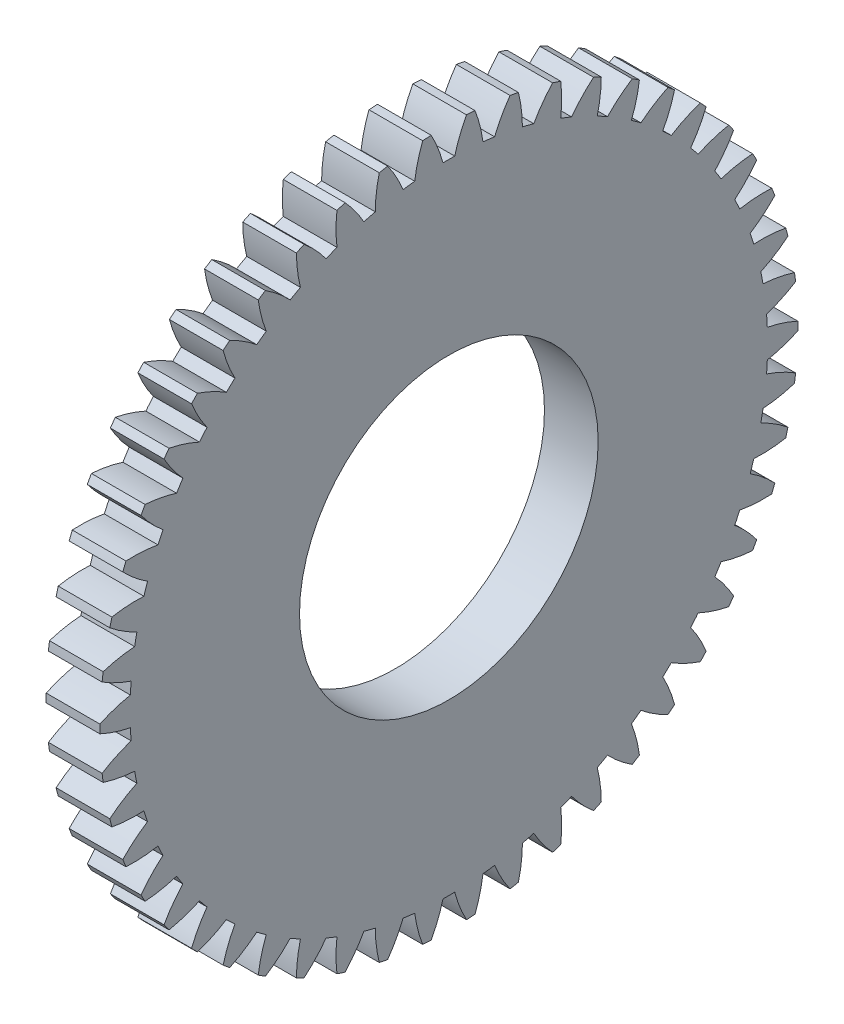
SolidWorks part; units mm, degrees
ref_plane "Plane1" through (0, 0, 0) normal (0, 0, 1) x (1, 0, 0)
ref_plane "Plane2" through (0, 0, 0) normal (0, 1, 0) x (1, 0, 0)
ref_plane "Plane3" through (0, 0, 0) normal (1, 0, 0) x (0, 0, -1)
sketch "HoldingSke" plane through (0, 0, 0) normal (0, 1, 0) x (1, 0, 0)
  line L0 (0, 0) -> (0.6428, -0.766)
  line L1 (-15, 0) -> (100, 0) construction
  line L2 (0, 0) -> (-2.1039, 2.3779)
  line L3 (0, 0) -> (-11.863, 4.5341)
  line L4 (0, 0) -> (5.5511, 6.6156)
  line L5 (0, 0) -> (-46.8476, -17.4728)
  line L6 (0, 0) -> (-3.3159, -2.2372)
  line L7 (-2.1039, 2.3779) -> (8.6586, 51.2059)
  line L8 (-76.2, 54.61) -> (-75.3, 54.61)
  line L9 (-71.009, 38.7566) -> (-53.1078, 45.2721)
  line L10 (-76.2, 71.12) -> (104.1128, 71.12)
  line L11 (0, 0) -> (-4, 0)
  line L12 (-76.2, 101.6) -> (-76.162, 101.6)
  line L13 (24.9733, 27.94) -> (52.9518, 28.4284)
  line L14 (24.9733, 27.94) -> (24.9743, 27.94)
  line L15 (24.9733, 27.94) -> (100.4006, 29.5858)
  line L16 (-63.627, -1) -> (-12.827, -1)
  circle A0 centre (0, 0) radius 2.5
  circle A1 centre (0, 0) radius 23.749
  circle A2 centre (0, 0) radius 37.5
  circle A3 centre (0, 0) radius 2.5
  dimension "MHD" = 47.498
  dimension "Hub_dia" = 75
  dimension "Bore" = 5
  dimension "MBD" = 5
  dimension "Num_teeth" = 50
  dimension "Pitch" = 1
  dimension "Overall_len" = 50
  dimension "Show_teeth" = 50
  dimension "Thickness" = 4
  dimension "OAL" = 50.0001
  dimension "T_dim" = 0.9
  dimension "Ap" = 20
  dimension "H" = 19.05
  dimension "Pitch_radius" = 180.3128
  dimension "Width" = 4
  dimension "Backlash" = 0.038
  dimension "Addendum_fac" = 1
  dimension "Dedendum_fac" = 1.25
  dimension "Clearance_fac" = 0.25
  dimension "Dedendum_add" = 0.001
  dimension "Module" = 1
sketch "BasProSke" plane through (0, 0, 0) normal (0, 1, 0) x (1, 0, 0)
  line L0 (-10, 0) -> (60, 0) construction
  line L1 (0, 0) -> (0, 26)
  line L2 (0, 0) -> (4, 0)
  line L3 (4, 0) -> (4, 26)
  line L4 (4, 26) -> (0, 26)
  dimension "Thickness" = 4
  dimension "Diameter" = 52
revolve "Base-Revolve" add sketch "BasProSke" angle 360 about L0
sketch "TooCutSke" plane through (0, 0, 0) normal (1, 0, 0) x (0, 0, -1)
  line L1 (0, 0) -> (0, 107) construction
  line L2 (0, 0) -> (-0.8518, 24.9855) construction
  line L3 (0, 0) -> (-3.1382, 49.8807) construction
  line L4 (-0.8518, 24.9855) -> (-1.5691, 24.9404) construction
  arc A0 (0.4377, 23.745) -> (-0.4377, 23.745) centre (0, 0) ccw
  arc A1 (1.3294, 25.9914) -> (-1.3294, 25.9914) centre (0, 0) ccw
  circle A2 centre (0, 0) radius 25 construction
  circle A3 centre (0, 0) radius 23.4923 construction
  arc A4 (-0.4377, 23.745) -> (-1.3294, 25.9914) centre (-10.1099, 21.2056) ccw
  arc A5 (1.3294, 25.9914) -> (0.4377, 23.745) centre (10.1099, 21.2056) ccw
  dimension "Root_dia" = 47.498
  dimension "Overcut_dia" = 52.0508
  dimension "Pitch_dia" = 50
  dimension "Base_dia" = 46.9846
  dimension "Flank_rad" = 10
  dimension "Half_ang" = 3.6
  dimension "Half_CT" = 0.7188
extrude "ToothCut" cut sketch "TooCutSke" along normal through all
fillet "Breaks" [suppressed] radius 0.02 tangent propagation no
fillet "RootFillets" [suppressed] radius 0.251
pattern_circular "TeethCuts" count 50 every 7.2 about axis through (-10, 0, 0) along (1, 0, 0) of "ToothCut", "RootFillets", "Breaks"
sketch "HubNeaOneSke" plane through (0, 0, 0) normal (-1, 0, 0) x (0, 0, 1)
  circle A0 centre (0, 0) radius 23.749
  dimension "Diameter" = 47.498
extrude "HubNearOne" [suppressed] add sketch "HubNeaOneSke" along normal blind 46.0001
sketch "HubNeaBotSke" plane through (0, 0, 0) normal (-1, 0, 0) x (0, 0, 1)
  circle A0 centre (0, 0) radius 23.749
  dimension "Diameter" = 47.498
extrude "HubNearBoth" [suppressed] add sketch "HubNeaBotSke" along normal blind 23
ref_plane "FarPln" through (4, 0, 0) normal (1, 0, 0) x (0, 0, -1)
sketch "HubFarSke" plane through (4, 0, 0) normal (1, 0, 0) x (0, 0, -1)
  circle A0 centre (0, 0) radius 23.749
  dimension "Diameter" = 47.498
extrude "HubFar" [suppressed] add sketch "HubFarSke" along normal blind 23
sketch "BorSke" plane through (0, 0, 0) normal (1, 0, 0) x (0, 0, -1)
  circle A0 centre (0, 0) radius 2.5
  dimension "Diameter" = 5
extrude "Bore" cut sketch "BorSke" along normal mid plane 100.0001
sketch "KeySke" plane through (0, 0, 0) normal (1, 0, 0) x (0, 0, -1)
  line L0 (-1, 0) -> (-1, 3.4)
  line L1 (-1, 3.4) -> (1, 3.4)
  line L2 (1, 3.4) -> (1, 0)
  line L3 (0, 0) -> (0, 34) construction
  line L4 (-1, 0) -> (1, 0)
  dimension "Offset" = 3.4
  dimension "Width" = 2
extrude "Keyway" [suppressed] cut sketch "KeySke" along normal mid plane 100.0001
pattern_circular "Keyway2" [suppressed] count 2 every 90 about axis through (-10, 0, 0) along (1, 0, 0) reverse direction yes
sketch "Sketch1" plane through (0, 0, 0) normal (-1, 0, 0) x (0, 0, 1)
  circle A0 centre (0, 0) radius 11.125
  circle A1 centre (0, 0) radius 2.5 construction
  dimension "D1" = 22.25
extrude "Cut-Extrude1" cut sketch "Sketch1" against normal up to next
equation "' \"Module@HoldingSke\" = 6.35"
equation "' \"Num_teeth@HoldingSke\" = 12"
equation "' \"Ap@HoldingSke\" =  20"
equation "' \"Ap@HoldingSke\" = 20"
equation "' \"Width@HoldingSke\" = 0.5 * 25.4"
equation "' \"Hub_dia@HoldingSke\"= 1 * 25.4"
equation "' \"Hub_dia@HoldingSke\" = 1 * 25.4"
equation "' \"Overall_len@HoldingSke\" = 1.0 * 25.4"
equation "' \"Bore@HoldingSke\" = 0.75 * 25.4"
equation "' \"T_dim@HoldingSke\" = 0.1 * 25.4"
equation "' \"Width@KeySke\" = 0.25 * 25.4"
equation "' \"Show_teeth@HoldingSke\" = 13"
equation "' \"Backlash@HoldingSke\" = 0.009 * 25.4"
equation "' \"Addendum_fac@HoldingSke\" = 1.0"
equation "' \"Dedendum_fac@HoldingSke\" = 1.25"
equation "' \"Dedendum_add@HoldingSke\" = 0.00005 * 25.4"
equation "' \"Clearance_fac@HoldingSke\" = 0.25"
equation "\"Pitch@HoldingSke\" = 1 / \"Module@HoldingSke\""
equation "\"Overcut_dia@TooCutSke\" = (\"Num_teeth@HoldingSke\" + 2 * \"Addendum_fac@HoldingSke\") / \"Pitch@HoldingSke\" + 0.002 * 25.4"
equation "\"Pitch_dia@TooCutSke\" = \"Num_teeth@HoldingSke\" / \"Pitch@HoldingSke\""
equation "\"Base_dia@TooCutSke\" = \"Num_teeth@HoldingSke\" / \"Pitch@HoldingSke\" * cos((\"Ap@HoldingSke\"  * 3.14159265 / 180))"
equation "\"Root_dia@TooCutSke\" = (\"Num_teeth@HoldingSke\" + 2) / \"Pitch@HoldingSke\" - 2 * (\"Addendum_fac@HoldingSke\" + \"Dedendum_fac@HoldingSke\") / \"Pitch@HoldingSke\" - \"Dedendum_add@HoldingSke\" * 2"
equation "\"Half_ang@TooCutSke\" = 180 / \"Num_teeth@HoldingSke\""
equation "\"Half_CT@TooCutSke\" = \"Num_teeth@HoldingSke\" / \"Pitch@HoldingSke\" * sin((3.14159265 / 2 / \"Num_teeth@HoldingSke\")) / 2 - 7 * \"Backlash@HoldingSke\" / 4"
equation "\"Flank_rad@TooCutSke\" = \"Num_teeth@HoldingSke\" / \"Pitch@HoldingSke\" / 5"
equation "\"Radius@RootFillets\" = \"Clearance_fac@HoldingSke\" / \"Pitch@HoldingSke\" + \"Dedendum_add@HoldingSke\""
equation "\"Break_rad@Breaks\" = 0.02 / \"Pitch@HoldingSke\""
equation "\"Thickness@HoldingSke\" = \"Width@HoldingSke\""
equation "\"OAL@HoldingSke\" = \"Thickness@HoldingSke\""
equation "\"MHD@HoldingSke\" = (\"Num_teeth@HoldingSke\" + 2) / \"Pitch@HoldingSke\" - 2 * (\"Addendum_fac@HoldingSke\" + \"Dedendum_fac@HoldingSke\")  / \"Pitch@HoldingSke\" - \"Dedendum_add@HoldingSke\" * 2"
equation "\"MBD@HoldingSke\" = (\"Num_teeth@HoldingSke\" + 2) / \"Pitch@HoldingSke\" - 2 * (\"Addendum_fac@HoldingSke\" + \"Dedendum_fac@HoldingSke\")  / \"Pitch@HoldingSke\" - \"Dedendum_add@HoldingSke\" * 2 - 0.002 * 25.4"
equation "\"MHD@HoldingSke\" = ((sgn( \"MHD@HoldingSke\" - \"Hub_dia@HoldingSke\" )-1)*( \"MHD@HoldingSke\" - \"Hub_dia@HoldingSke\" ))/-2+ \"Hub_dia@HoldingSke\""
equation "\"MBD@HoldingSke\" = ((sgn( \"MBD@HoldingSke\" - \"Bore@HoldingSke\" )-1)*( \"MBD@HoldingSke\" - \"Bore@HoldingSke\" ))/-2+ \"Bore@HoldingSke\""
equation "\"OAL@HoldingSke\" = ((sgn( \"OAL@HoldingSke\" - \"Overall_len@HoldingSke\" )+1)*( \"OAL@HoldingSke\" - \"Overall_len@HoldingSke\" ))/2 + \"Overall_len@HoldingSke\" + 0.000002 * 25.4"
equation "\"Num_teeth@TeethCuts\" = int( \"Show_teeth@HoldingSke\" ) + 1"
equation "\"Num_teeth@TeethCuts\" = ((sgn( \"Num_teeth@TeethCuts\" - \"Num_teeth@HoldingSke\" )-1)*( \"Num_teeth@TeethCuts\" - \"Num_teeth@HoldingSke\" ))/-2+ \"Num_teeth@HoldingSke\""
equation "\"Num_teeth@TeethCuts\" = ((sgn( \"Num_teeth@TeethCuts\" - 2.0)+1)*( \"Num_teeth@TeethCuts\" - 2.0))/2 +2.0"
equation "\"Angle@TeethCuts\" = 360.0 / \"Num_teeth@HoldingSke\""
equation "\"Diameter@BasProSke\" = (\"Num_teeth@HoldingSke\" + 2 * \"Addendum_fac@HoldingSke\") / \"Pitch@HoldingSke\""
equation "\"Thickness@BasProSke\"  = \"Thickness@HoldingSke\""
equation "' \"Fillet_rad@BasProSke\" =  \"Thickness@HoldingSke\" * 0.05"
equation "' \"Fillet_rad@BasProSke\" = \"Thickness@HoldingSke\" * 0.05"
equation "\"MHD@HoldingSke\" = ((sgn( \"MHD@HoldingSke\" - \"Root_dia@TooCutSke\" )-1)*( \"MHD@HoldingSke\" - \"Root_dia@TooCutSke\" ))/-2+ \"Root_dia@TooCutSke\""
equation "\"Diameter@HubNeaOneSke\" = \"MHD@HoldingSke\""
equation "\"Length@HubNearOne\" = \"OAL@HoldingSke\" - \"Thickness@BasProSke\""
equation "\"Diameter@HubNeaBotSke\" = \"MHD@HoldingSke\""
equation "\"Length@HubNearBoth\" = ( \"OAL@HoldingSke\" - \"Thickness@BasProSke\" ) / 2.0"
equation "\"Thickness@FarPln\" = \"Thickness@BasProSke\""
equation "\"Diameter@HubFarSke\" = \"MHD@HoldingSke\""
equation "\"Length@HubFar\" = ( \"OAL@HoldingSke\" - \"Thickness@BasProSke\" ) / 2.0"
equation "\"Diameter@BorSke\" = \"MBD@HoldingSke\""
equation "\"D1@Bore\" = \"OAL@HoldingSke\" * 2.0"
equation "\"D1@Keyway\" = \"OAL@HoldingSke\" * 2.0"
equation "\"Offset@KeySke\" = \"T_dim@HoldingSke\" + \"MBD@HoldingSke\" / 2.0"
